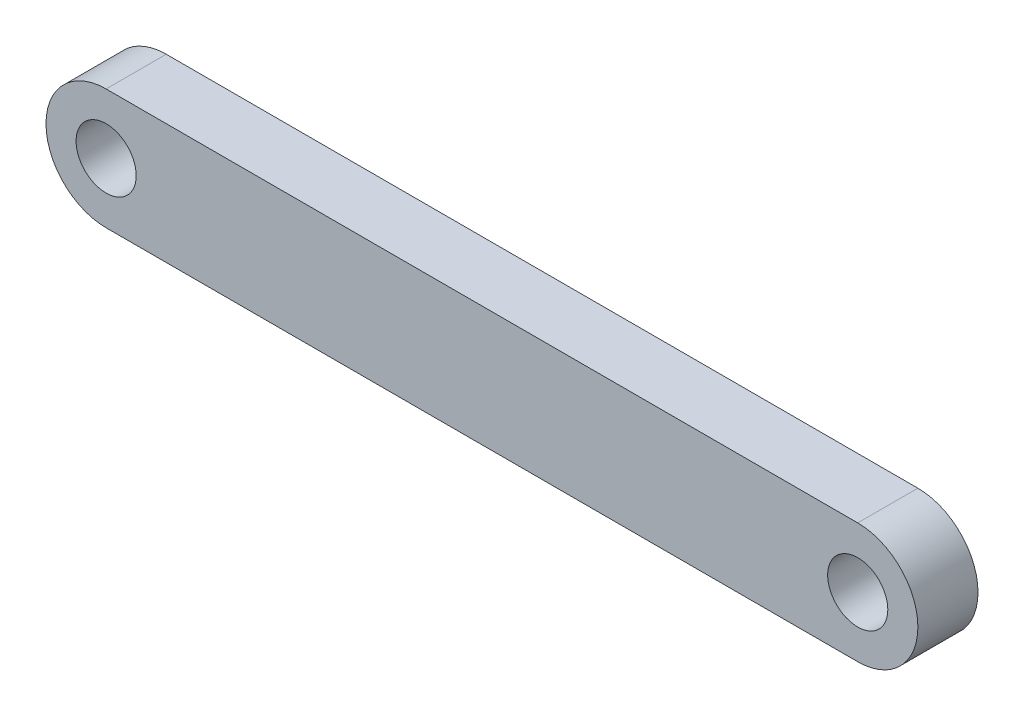
SolidWorks part; units mm, degrees
ref_plane "Front Plane" through (0, 0, 0) normal (0, 0, 1) x (1, 0, 0)
ref_plane "Top Plane" through (0, 0, 0) normal (0, 1, 0) x (1, 0, 0)
ref_plane "Right Plane" through (0, 0, 0) normal (1, 0, 0) x (0, 0, -1)
sketch "Sketch1" plane through (0, 0, 0) normal (0, 0, 1) x (1, 0, 0)
  line L0 (-15.875, 0) -> (15.875, 0) construction
  line L1 (-15.875, 2.54) -> (15.875, 2.54)
  line L2 (-15.875, -2.54) -> (15.875, -2.54)
  arc A0 (-15.875, 2.54) -> (-15.875, -2.54) centre (-15.875, 0) ccw
  arc A1 (15.875, -2.54) -> (15.875, 2.54) centre (15.875, 0) ccw
  circle A2 centre (-15.875, 0) radius 1.27
  circle A3 centre (15.875, 0) radius 1.27
  point P2 (0, 0)
  dimension "D2" = 2.54
  dimension "D3" = 2.54
  dimension "D1" = 31.75
extrude "Boss-Extrude1" add sketch "Sketch1" along normal blind 1.27 and the other way blind 1.27
